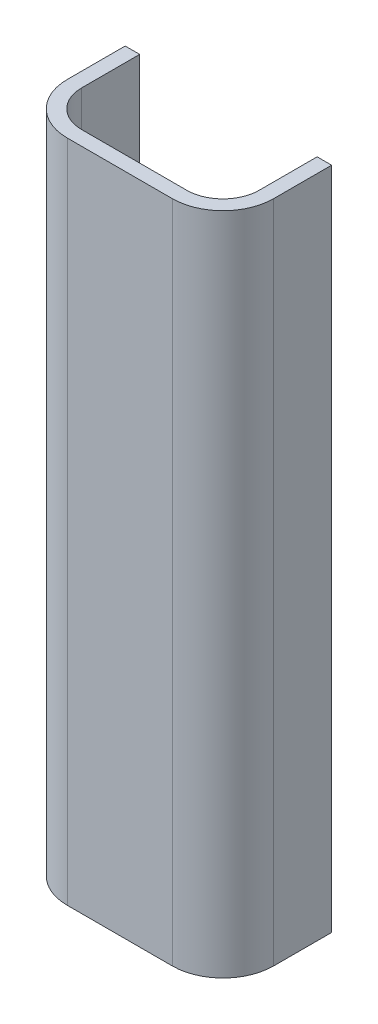
SolidWorks part; units mm, degrees
ref_plane "Front Plane" through (0, 0, 0) normal (0, 0, 1) x (1, 0, 0)
ref_plane "Top Plane" through (0, 0, 0) normal (0, 1, 0) x (1, 0, 0)
ref_plane "Right Plane" through (0, 0, 0) normal (1, 0, 0) x (0, 0, -1)
sketch "Sketch1" plane through (0, 0, 0) normal (0, 0, 1) x (1, 0, 0)
  line L0 (-10.5, 67.5) -> (-22.5, 67.5) construction
  line L1 (-10.5, 67.5) -> (-10.5, -67.5) construction
  line L2 (-22.5, -67.5) -> (-10.5, -67.5) construction
  line L3 (10.5, 67.5) -> (-10.5, 67.5) construction
  line L4 (-10.5, -67.5) -> (10.5, -67.5) construction
  line L5 (22.5, 67.5) -> (10.5, 67.5) construction
  line L6 (10.5, -67.5) -> (22.5, -67.5) construction
  line L7 (10.5, -67.5) -> (10.5, 67.5) construction
  line L8 (-10.5, 67.5) -> (-22.5, 67.5)
  line L9 (-10.5, 67.5) -> (-10.5, -67.5)
  line L10 (-22.5, -67.5) -> (-10.5, -67.5)
  line L11 (10.5, 67.5) -> (-10.5, 67.5)
  line L12 (-10.5, -67.5) -> (10.5, -67.5)
  line L13 (22.5, 67.5) -> (10.5, 67.5)
  line L14 (10.5, -67.5) -> (22.5, -67.5)
  line L15 (10.5, -67.5) -> (10.5, 67.5)
  line L16 (-28.5, 110) -> (-28.5, -73.5)
  line L17 (-24.5, 106) -> (24.5, 106)
  line L18 (-24.5, 106) -> (-24.5, -69.5)
  line L19 (-24.5, -69.5) -> (24.5, -69.5)
  line L20 (24.5, 106) -> (24.5, -69.5)
  line L21 (-28.5, -73.5) -> (28.5, -73.5)
  line L22 (28.5, 110) -> (28.5, -73.5)
  line L23 (-28.5, 110) -> (28.5, 110)
  circle A0 centre (0, 90) radius 10 construction
  dimension "D4" = 16
  dimension "D1" = 2
  dimension "D2" = 2
  dimension "D3" = 2
  dimension "D5" = 4
extrude "Boss-Extrude1" add sketch "Sketch1" along normal offset from surface (30 mm away) 6 contours L23 L16 L21 L22 L17 L20 L19 L18 region at (0, 108.0785, 0) offset beyond the face yes
sketch "Sketch2" plane through (0, -69.5, 0) normal (0, 1, 0) x (1, 0, 0)
  line L0 (-24.5, -30) -> (-24.5, 0) construction
  line L1 (24.5, -30) -> (-24.5, -30)
  line L2 (24.5, -30) -> (24.5, -26)
  line L3 (24.5, -26) -> (-24.5, -26)
  line L4 (-24.5, -30) -> (-24.5, -26)
  line L5 (24.5, -30) -> (24.5, 0) construction
  line L6 (24.5, -16) -> (24.5, -26)
  line L7 (-24.5, -16) -> (-24.5, -26)
  line L8 (24.5, -16) -> (24.5, 0)
  line L9 (24.5, 0) -> (-24.5, 0)
  line L10 (-24.5, 0) -> (-24.5, -16)
  arc A0 (24.5, -16) -> (14.5, -26) centre (14.5, -16) cw
  arc A1 (-14.5, -26) -> (-24.5, -16) centre (-14.5, -16) cw
  line M5 (-24.5, -30) -> (24.5, -30)
  line M6 (24.5, -30) -> (24.5, 0)
  line M7 (24.5, 0) -> (-24.5, 0)
  line M8 (-24.5, 0) -> (-24.5, -30)
  dimension "D2" = 10
  dimension "D3" = 10
  dimension "D1" = 4
extrude "Boss-Extrude2" add sketch "Sketch2" along normal up to surface (175.5 mm away) contours A0 L3 M6 | L3 M6 M8 M5 | L3 A1 M8 region at (0, -69.5, 28) region at (22.2663, -69.5, 23.7663) region at (-22.2663, -69.5, 23.7663) up to face at (0, 106, 15)
fillet "Fillet1" radius 14 2 edges at (28.5, 18.25, 30) (-28.5, 18.25, 30)
extrude "Cut-Extrude1" cut sketch "Sketch2<4>" along normal up to surface (179.5 mm away) contours A1 L3 A0 M6 M7 M8 region at (0, -69.5, 12.6246) up to face at (0, 110, 16.2998)
sketch "Sketch2<4>" plane through (0, -69.5, 0) normal (0, 1, 0) x (1, 0, 0) same geometry as "Sketch2"
